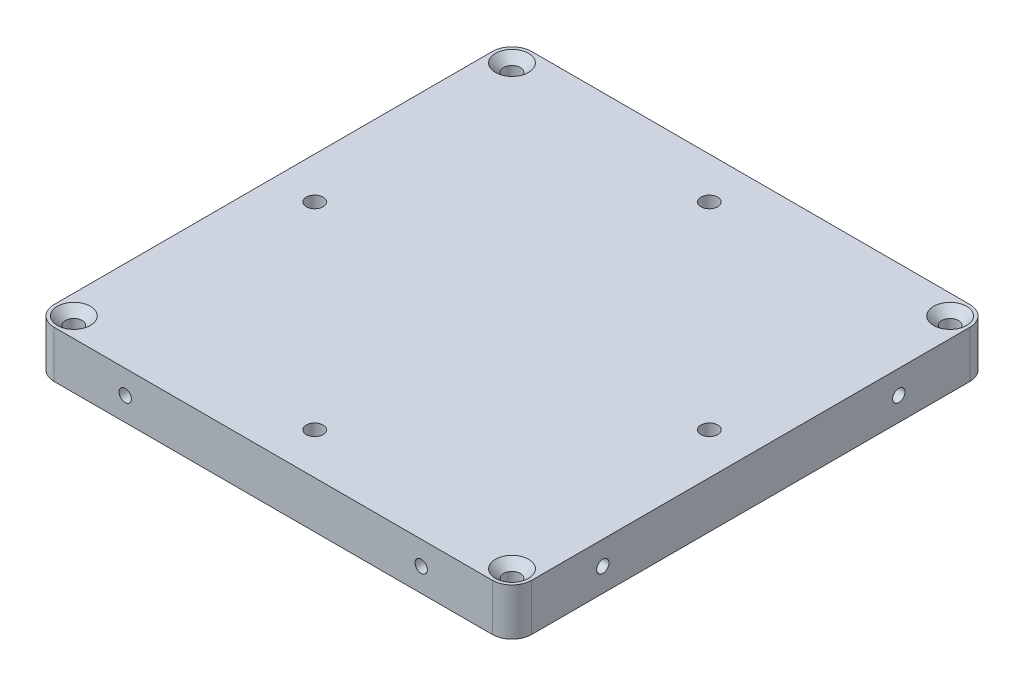
SolidWorks part; units mm, degrees
material "6061-T6 (SS)"
ref_plane "Front Plane" through (0, 0, 0) normal (0, 0, 1) x (1, 0, 0)
ref_plane "Top Plane" through (0, 0, 0) normal (0, 1, 0) x (1, 0, 0)
ref_plane "Right Plane" through (0, 0, 0) normal (1, 0, 0) x (0, 0, -1)
sketch "Sketch1" plane through (0, 0, 0) normal (0, 1, 0) x (1, 0, 0)
  line L1 (48.4125, -48.4125) -> (-48.4125, -48.4125)
  line L2 (48.4125, -48.4125) -> (48.4125, 48.4125)
  line L3 (48.4125, 48.4125) -> (-48.4125, 48.4125)
  line L4 (-48.4125, -48.4125) -> (-48.4125, 48.4125)
  line L5 (48.4125, -48.4125) -> (-48.4125, 48.4125) construction
  line L6 (48.4125, 48.4125) -> (-48.4125, -48.4125) construction
  point P0 (0, 0)
  dimension "D1" = 96.825
extrude "Boss-Extrude1" add sketch "Sketch1" along normal mid plane 9.525
fillet "Fillet1" radius 4 4 edges at (-48.4125, 0, -48.4125) (48.4125, 0, -48.4125) (48.4125, 0, 48.4125) (-48.4125, 0, 48.4125)
sketch "Sketch4" plane through (0, -4.7625, 0) normal (0, 1, 0) x (1, 0, 0)
  point P0 (-40, 0)
  point P2 (0, 40)
  point P4 (40, 0)
  point P6 (0, -40)
  dimension "D1" = 40
  dimension "D2" = 40
  dimension "D3" = 40
  dimension "D4" = 40
hole_wizard "CSK for M3 SFHCS2" positions "Sketch4" profile "Sketch3" countersink size "M3" standard "ANSI Metric" end condition through all
sketch "Sketch3" plane through (-40, -4.7625, 0) normal (1, 0, 0) x (0, 0, -1)
  line L0 (0, 0) -> (0, 9.525)
  line L1 (0, 9.525) -> (1.7, 9.525)
  line L2 (1.7, 9.525) -> (1.7, 1.66)
  line L3 (1.7, 1.66) -> (3.36, 0)
  line L5 (3.36, 0) -> (0, 0)
  line L6 (-1.7, 1.66) -> (-3.36, 0) construction
  line L11 (0, -6.35) -> (0, 107.95) construction
  dimension "Thru Hole Dia." = 3.4
  dimension "Thru Hole Depth" = 9.525
  dimension "Near C'Sink Dia." = 6.72
  dimension "Near C'Sink Angle" = 90
sketch "Sketch7" plane through (0, 4.7625, 0) normal (0, 1, 0) x (1, 0, 0)
  arc A0 (-44.4125, 48.4125) -> (-48.4125, 44.4125) centre (-44.4125, 44.4125) ccw construction
  arc A1 (-48.4125, -44.4125) -> (-44.4125, -48.4125) centre (-44.4125, -44.4125) ccw construction
  arc A2 (48.4125, 44.4125) -> (44.4125, 48.4125) centre (44.4125, 44.4125) ccw construction
  arc A3 (44.4125, -48.4125) -> (48.4125, -44.4125) centre (44.4125, -44.4125) ccw construction
  point P0 (-44.4125, 44.4125)
  point P2 (44.4125, 44.4125)
  point P4 (44.4125, -44.4125)
  point P6 (-44.4125, -44.4125)
hole_wizard "CSK for M3 SFHCS1" positions "Sketch7" profile "Sketch6" countersink size "M3" standard "ANSI Metric"
sketch "Sketch6" plane through (-44.4125, 4.7625, -44.4125) normal (1, 0, 0) x (0, 0, 1)
  line L0 (0, 0) -> (0, 36.0215)
  line L1 (0, 36.0215) -> (1.7, 35)
  line L2 (1.7, 35) -> (1.7, 1.66)
  line L3 (1.7, 1.66) -> (3.36, 0)
  line L5 (3.36, 0) -> (0, 0)
  line L6 (-1.7, 1.66) -> (-3.36, 0) construction
  line L10 (0, 36.0215) -> (-1.7, 35) construction
  line L11 (0, -6.35) -> (0, 107.95) construction
  dimension "Hole Dia." = 3.4
  dimension "Hole Depth" = 35
  dimension "Near C'Sink Dia." = 6.72
  dimension "Near C'Sink Angle" = 90
  dimension "Drill Angle" = 118
sketch "Sketch10" plane through (0, 0, 48.4125) normal (0, 0, 1) x (1, 0, 0)
  point P0 (-30, 0)
  point P2 (30, 0)
  dimension "D1" = 30
  dimension "D2" = 30
hole_wizard "M3x0.5 Tapped Hole1" positions "Sketch10" profile "Sketch11" tap size "M3x0.5" standard "ANSI Metric"
sketch "Sketch11" plane through (-30, 0, 48.4125) normal (1, 0, 0) x (0, -1, 0)
  line L0 (0, 0) -> (0, 10.7511)
  line L1 (0, 10.7511) -> (1.25, 10)
  line L2 (1.25, 10) -> (1.25, 0)
  line L5 (1.25, 0) -> (0, 0)
  line L10 (0, 10.7511) -> (-1.25, 10) construction
  line L11 (0, -6.35) -> (0, 107.95) construction
  dimension "Tap Drill Dia." = 2.5
  dimension "Tap Drill Depth" = 10
  dimension "Drill Angle" = 118
sketch "Sketch14" plane through (-48.4125, 0, 0) normal (-1, 0, 0) x (0, 0, 1)
  point P0 (-30, 0)
  point P2 (30, 0)
  dimension "D1" = 30
  dimension "D2" = 30
hole_wizard "M3x0.5 Tapped Hole2" positions "Sketch14" profile "Sketch13" tap size "M3x0.5" standard "ANSI Metric"
sketch "Sketch13" plane through (-48.4125, 0, -30) normal (0, 1, 0) x (0, 0, 1)
  line L0 (0, 0) -> (0, 10.7511)
  line L1 (0, 10.7511) -> (1.25, 10)
  line L2 (1.25, 10) -> (1.25, 0)
  line L5 (1.25, 0) -> (0, 0)
  line L10 (0, 10.7511) -> (-1.25, 10) construction
  line L11 (0, -6.35) -> (0, 107.95) construction
  dimension "Tap Drill Dia." = 2.5
  dimension "Tap Drill Depth" = 10
  dimension "Drill Angle" = 118
sketch "Sketch17" plane through (0, 0, -48.4125) normal (0, 0, -1) x (-1, 0, 0)
  point P0 (-30, 0)
  point P2 (30, 0)
  point P5 (0, 0)
  dimension "D1" = 30
  dimension "D2" = 30
hole_wizard "M3x0.5 Tapped Hole3" positions "Sketch17" profile "Sketch16" tap size "M3x0.5" standard "ANSI Metric"
sketch "Sketch16" plane through (30, 0, -48.4125) normal (1, 0, 0) x (0, 1, 0)
  line L0 (0, 0) -> (0, 10.7511)
  line L1 (0, 10.7511) -> (1.25, 10)
  line L2 (1.25, 10) -> (1.25, 0)
  line L5 (1.25, 0) -> (0, 0)
  line L10 (0, 10.7511) -> (-1.25, 10) construction
  line L11 (0, -6.35) -> (0, 107.95) construction
  dimension "Tap Drill Dia." = 2.5
  dimension "Tap Drill Depth" = 10
  dimension "Drill Angle" = 118
sketch "Sketch20" plane through (48.4125, 0, 0) normal (1, 0, 0) x (0, 0, -1)
  point P0 (-30, 0)
  point P2 (30, 0)
  point P5 (0, 0)
  dimension "D1" = 30
  dimension "D2" = 30
hole_wizard "M3x0.5 Tapped Hole4" positions "Sketch20" profile "Sketch19" tap size "M3x0.5" standard "ANSI Metric"
sketch "Sketch19" plane through (48.4125, 0, 30) normal (0, 1, 0) x (0, 0, -1)
  line L0 (0, 0) -> (0, 10.7511)
  line L1 (0, 10.7511) -> (1.25, 10)
  line L2 (1.25, 10) -> (1.25, 0)
  line L5 (1.25, 0) -> (0, 0)
  line L10 (0, 10.7511) -> (-1.25, 10) construction
  line L11 (0, -6.35) -> (0, 107.95) construction
  dimension "Tap Drill Dia." = 2.5
  dimension "Tap Drill Depth" = 10
  dimension "Drill Angle" = 118
